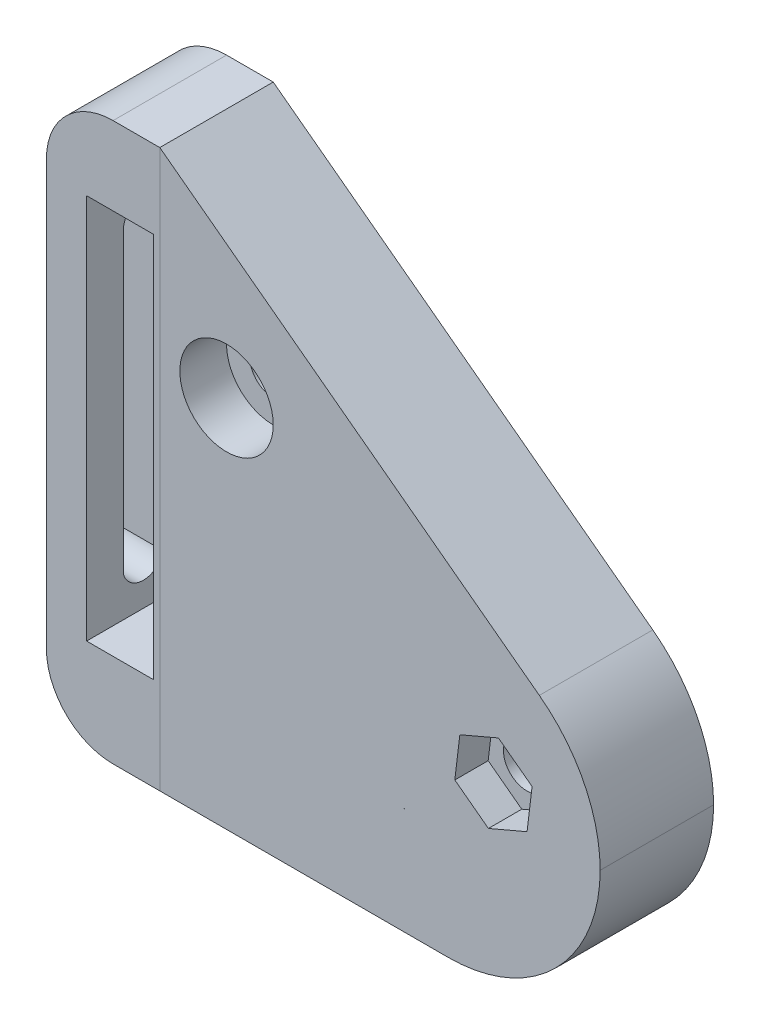
SolidWorks part; units mm, degrees
ref_plane "Front Plane" through (0, 0, 0) normal (0, 0, 1) x (1, 0, 0)
ref_plane "Top Plane" through (0, 0, 0) normal (0, 1, 0) x (1, 0, 0)
ref_plane "Right Plane" through (0, 0, 0) normal (1, 0, 0) x (0, 0, -1)
sketch "Sketch1" plane through (0, 0, 0) normal (0, 0, 1) x (1, 0, 0)
  line L5 (0, -14) -> (-20, 1) construction
  line L37 (8, -10) -> (8, -27)
  line L38 (-25, -27) -> (-25, 14.75)
  line L41 (-25, 14.75) -> (8, -10)
  line L48 (-25, -27) -> (8, -27)
  line L50 (-6.6879, -19) -> (-6.6667, -19)
  line L52 (-6.6667, -19) -> (-6.6879, -18.9841)
  line L54 (-6.6879, -18.9841) -> (-6.6879, -19)
  circle A1 centre (-20, 1) radius 1.75
  circle A2 centre (0, -14) radius 1.75
  dimension "D6" = 3.5
  dimension "D5" = 8
  dimension "D17" = 19
  dimension "D4" = 8
  dimension "D1" = 15
  dimension "D2" = 5
  dimension "D7" = 14
  dimension "D8" = 20
  dimension "D9" = 20
  dimension "D10" = 8
  dimension "D13" = 8
extrude "Boss-Extrude1" add sketch "Sketch1" along normal blind 8.5
sketch "Sketch3" plane through (0, 0, 0) normal (0, 0, -1) x (-1, 0, 0)
  line L0 (25, 14.75) -> (25, -27) construction
  line L1 (22.725, 2.5733) -> (20, 4.1466)
  line L2 (20, 4.1466) -> (17.275, 2.5733)
  line L3 (17.275, 2.5733) -> (17.275, -0.5733)
  line L4 (17.275, -0.5733) -> (20, -2.1466)
  line L5 (20, -2.1466) -> (22.725, -0.5733)
  line L6 (22.725, -0.5733) -> (22.725, 2.5733)
  circle A0 centre (20, 1) radius 2.725 construction
  dimension "D1" = 5.45
extrude "Cut-Extrude2" cut sketch "Sketch3" against normal blind 2.5
sketch "Sketch4" plane through (0, 0, 8.5) normal (0, 0, 1) x (1, 0, 0)
  line L0 (8, -10) -> (-25, 14.75) construction
  line L1 (-2.5172, -12.1121) -> (-2.8936, -15.236)
  line L2 (-2.8936, -15.236) -> (-0.3764, -17.124)
  line L3 (-0.3764, -17.124) -> (2.5172, -15.8879)
  line L4 (2.5172, -15.8879) -> (2.8936, -12.764)
  line L5 (2.8936, -12.764) -> (0.3764, -10.876)
  line L6 (0.3764, -10.876) -> (-2.5172, -12.1121)
  circle A0 centre (0, -14) radius 2.725 construction
  dimension "D1" = 5.45
extrude "Cut-Extrude3" cut sketch "Sketch4" against normal blind 2.5
sketch "Sketch5" plane through (0, 0, 8.5) normal (0, 0, 1) x (1, 0, 0)
  circle A0 centre (-20, 1) radius 3.5
  dimension "D1" = 7
extrude "Cut-Extrude4" cut sketch "Sketch5" against normal blind 3.5
sketch "Sketch6" plane through (0, 0, 0) normal (0, 0, -1) x (-1, 0, 0)
  circle A0 centre (0, -14) radius 3.5
  dimension "D1" = 7
extrude "Cut-Extrude5" cut sketch "Sketch6" against normal blind 3.5
sketch "Sketch7" plane through (-25, 0, 0) normal (-1, 0, 0) x (0, 0, 1)
  line L6 (8.5, -27) -> (0, -27) construction
  line L7 (-0.0008, -27) -> (8.5008, -27)
  line L8 (-0.0008, -27) -> (-0.0008, 14.75)
  line L9 (-0.0008, 14.75) -> (8.5008, 14.75)
  line L10 (8.5008, -27) -> (8.5008, 14.75)
  line L11 (8.5, 14.75) -> (0, 14.75) construction
  point P6 (4.25, -27)
  point P7 (4.25, -27)
  dimension "D1" = 8.5017
fillet "Fillet1" radius 11.4 2 edges at (8, -10, 4.25) (8, -27, 4.25)
extrude "Boss-Extrude3" add sketch "Sketch7" along normal blind 8.5
sketch "Sketch8" plane through (0, 0, 8.5008) normal (0, 0, 1) x (1, 0, 0)
  line L2 (-30.4832, 8.8854) -> (-25.4832, 8.8854)
  line L3 (-30.4832, 8.8854) -> (-30.4832, -20.0171)
  line L4 (-30.4832, -20.0171) -> (-25.4832, -20.0171)
  line L5 (-25.4832, 8.8854) -> (-25.4832, -20.0171)
extrude "Cut-Extrude6" cut sketch "Sketch8" against normal through all
sketch "Sketch9" plane through (-33.5, 0, 0) normal (-1, 0, 0) x (0, 0, 1)
  line L9 (5.75, -17.0383) -> (5.75, 5.276)
  line L12 (2.75, 5.276) -> (2.75, -17.0383)
  arc A0 (5.75, -17.0383) -> (2.75, -17.0383) centre (4.25, -16.6439) cw
  arc A1 (5.75, 5.276) -> (2.75, 5.276) centre (4.25, 5.276) ccw
extrude "Cut-Extrude7" cut sketch "Sketch9" against normal up to next
fillet "Fillet2" radius 5 1 edges at (-33.5, -27, 4.25)
fillet "Fillet3" radius 5 1 edges at (-33.5, 14.75, 4.25)
